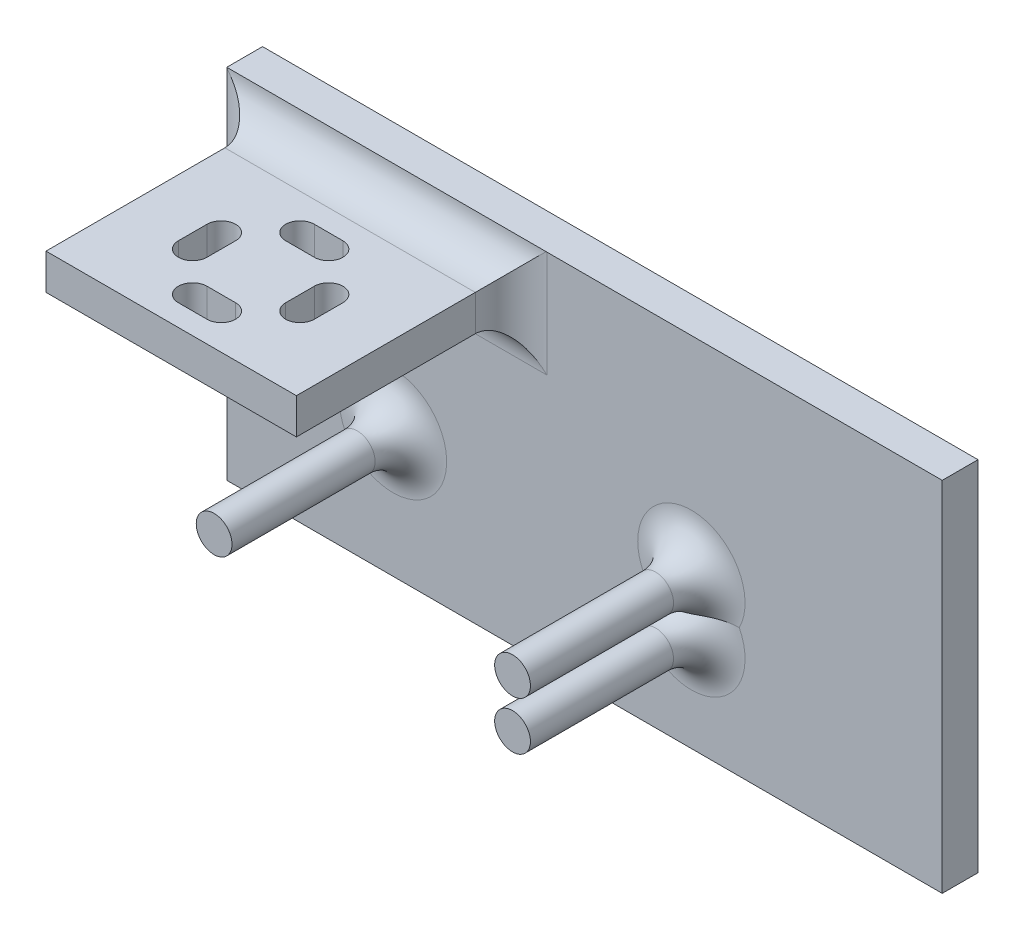
SolidWorks part; units mm, degrees
note: '?' marks a value the reader was unsure of.
ref_plane "Front Plane" through (0, 0, 0) normal (0, 0, 1) x (1, 0, 0)
ref_plane "Top Plane" through (0, 0, 0) normal (0, 1, 0) x (1, 0, 0)
ref_plane "Right Plane" through (0, 0, 0) normal (1, 0, 0) x (0, 0, -1)
sketch "Sketch1" plane through (0, 0, 0) normal (0, 0, 1) x (1, 0, 0)
  line L1 (-25.4, -12.7) -> (25.4, -12.7)
  line L2 (-25.4, -12.7) -> (-25.4, 12.7)
  line L3 (-25.4, 12.7) -> (25.4, 12.7)
  line L4 (25.4, -12.7) -> (25.4, 12.7)
  line L5 (-25.4, -12.7) -> (25.4, 12.7) construction
  line L6 (-25.4, 12.7) -> (25.4, -12.7) construction
  point P0 (0, 0)
  dimension "D1" = 25.4
  dimension "D2" = 50.8
extrude "base" add sketch "Sketch1" along normal blind 2.54
sketch "Sketch2" plane through (0, 0, 2.54) normal (0, 0, 1) x (1, 0, 0)
  circle A0 centre (7.5903, -1.8468) radius 1.27
  circle A1 centre (7.5903, -5.2853) radius 1.27
  circle A2 centre (-13.5976, -3.7518) radius 1.27
  dimension "D1" = 2.54
  dimension "D2" = 2.54
  dimension "D4" = 2.54
  dimension "D3" = 0
  dimension "D5" = 1.905
extrude "guideposts" add sketch "Sketch2" along normal blind 12.7
sketch "Sketch3" plane through (0, 0, 2.54) normal (0, 0, 1) x (1, 0, 0)
  line L1 (-22.9956, 7.6782) -> (-5.2156, 7.6782)
  line L2 (-22.9956, 7.6782) -> (-22.9956, 10.2182)
  line L3 (-22.9956, 10.2182) -> (-5.2156, 10.2182)
  line L4 (-5.2156, 7.6782) -> (-5.2156, 10.2182)
  line L5 (-22.9956, 7.6782) -> (-5.2156, 10.2182) construction
  line L6 (-22.9956, 10.2182) -> (-5.2156, 7.6782) construction
  circle A0 centre (-13.5976, -3.7518) radius 1.27 construction
  circle A1 centre (-13.5976, -3.7518) radius 1.27 construction
  point P0 (-14.1056, 8.9482)
  dimension "D3" = 12.7
  dimension "D1" = 17.78
  dimension "D2" = 2.54
  dimension "D4" = 0.508
extrude "button holder" add sketch "Sketch3" along normal blind 15.24
fillet "round on button holder" radius 2.54 7 edges at (-14.1056, 10.2182, 2.54) (-22.9956, 8.9482, 2.54) (-14.1056, 7.6782, 2.54) (-5.2156, 8.9482, 2.54) (6.3203, -1.8468, 2.54) (6.3203, -5.2853, 2.54) (-14.8676, -3.7518, 2.54)
ref_point "button center"
sketch "Sketch4" plane through (0, 10.2182, 0) normal (0, 1, 0) x (1, 0, 0)
  line L0 (-15.1216, -15.24) -> (-13.0896, -15.24) construction
  line L1 (-15.1216, -14.224) -> (-13.0896, -14.224)
  line L2 (-15.1216, -16.256) -> (-13.0896, -16.256)
  line L3 (-5.2156, -17.78) -> (-5.2156, -5.08) construction
  line L4 (-5.2156, -17.78) -> (-22.9956, -17.78) construction
  arc A0 (-15.1216, -14.224) -> (-15.1216, -16.256) centre (-15.1216, -15.24) ccw
  arc A1 (-13.0896, -16.256) -> (-13.0896, -14.224) centre (-13.0896, -15.24) ccw
  point P2 (-14.1056, -15.24)
  point P9 (-14.1056, -17.78)
  dimension "D1" = 1.016
  dimension "D2" = 2.032
  dimension "D3" = 8.89
  dimension "D4" = 2.54
extrude "one button leg hole" cut sketch "Sketch4" against normal up to next
ref_axis "button axis" through (-14.1056, 10.2182, 11.4297) along (0, 1, 0)?
pattern_circular "button leg holes" count 4 over 360 about axis through (-14.1056, 0, 11.4297) along (0, 1, 0) of "one button leg hole"
